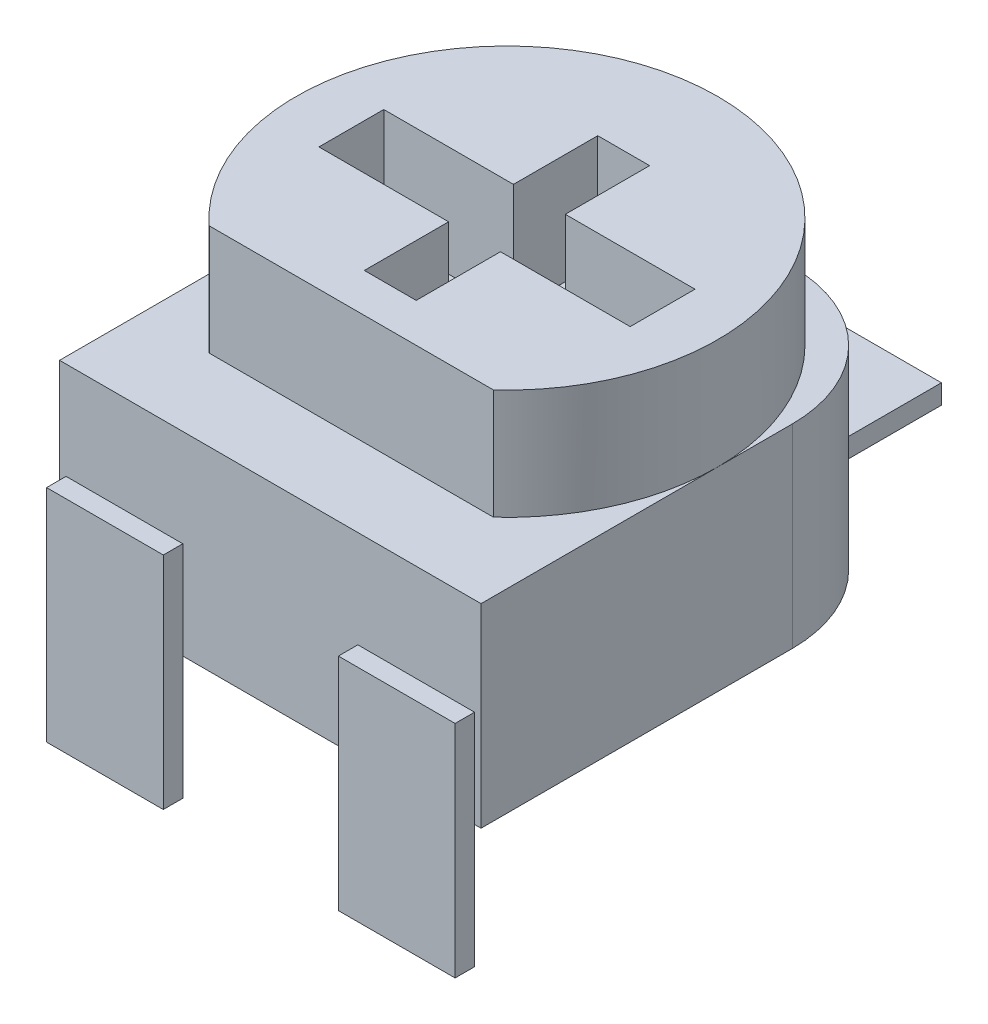
SolidWorks part; units mm, degrees
note: The reader was unsure of these and kept them because the rebuilt part matched: shared geometry of "草图1<3>", "草图1<4>".
ref_plane "前视基准面" through (0, 0, 0) normal (0, 0, 1) x (1, 0, 0)
ref_plane "上视基准面" through (0, 0, 0) normal (0, 1, 0) x (1, 0, 0)
ref_plane "右视基准面" through (0, 0, 0) normal (1, 0, 0) x (0, 0, -1)
other "Configuration Table"
sketch "草图1" plane through (0, 0, 0) normal (0, 1, 0) x (1, 0, 0)
  line L0 (-2.1915, -2.4) -> (2.1915, -2.4)
  line L1 (-3.25, 3.25) -> (3.25, 3.25)
  line L2 (-3.25, 3.25) -> (-3.25, -3.65)
  line L3 (-3.25, -3.65) -> (3.25, -3.65)
  line L4 (3.25, 3.25) -> (3.25, -3.65)
  line L5 (0, 3.25) -> (0, -3.65) construction
  line L6 (-2.4, -0.5) -> (2.4, -0.5)
  line L7 (-2.4, -0.5) -> (-2.4, 0.5)
  line L8 (-2.4, 0.5) -> (2.4, 0.5)
  line L9 (2.4, -0.5) -> (2.4, 0.5)
  line L10 (-2.4, -0.5) -> (2.4, 0.5) construction
  line L11 (-2.4, 0.5) -> (2.4, -0.5) construction
  line L12 (-0.4, -1.8) -> (0.4, -1.8)
  line L13 (-0.4, -1.8) -> (-0.4, 1.8)
  line L14 (-0.4, 1.8) -> (0.4, 1.8)
  line L15 (0.4, -1.8) -> (0.4, 1.8)
  line L16 (-0.4, -1.8) -> (0.4, 1.8) construction
  line L17 (-0.4, 1.8) -> (0.4, -1.8) construction
  circle A0 centre (0, 0) radius 3.25
  circle A1 centre (0, 0) radius 1.8
  dimension "D4" = 1.25
  dimension "D1" = 3.25
  dimension "D2" = 3.65
  dimension "D3" = 6.5
  dimension "D5" = 0.8
  dimension "D6" = 1
  dimension "D7" = 4.8
  dimension "D8" = 3.6
extrude "凸台-拉伸1" add sketch "草图1" along normal blind 3 contours L4 L3 L2 L1
extrude "凸台-拉伸2" add sketch "草图1<3>" along normal blind 1.7 from surface at 3 contours A0 | L6 L9 L8 L7 | L13 L14 L15 L12
sketch "草图1<3>" plane through (0, 0, 0) normal (0, 1, 0) x (1, 0, 0) same geometry as "草图1"
extrude "切除-拉伸1" cut sketch "草图1<4>" against normal up to surface (1.7 mm away) from surface at 4.7 contours L0 A0 up to face at (0, 3, 2.6375) starting at face at (0, 4.7, -3.25)
sketch "草图1<4>" plane through (0, 0, 0) normal (0, 1, 0) x (1, 0, 0) same geometry as "草图1"
fillet "圆角1" radius 2.1 2 edges at (3.25, 1.5, -3.25) (-3.25, 1.5, -3.25)
sketch "草图2" plane through (0, 0, 3.65) normal (0, 0, 1) x (1, 0, 0)
  line L0 (-3.25, 1.5) -> (3.25, 1.5)
  line L1 (-3.25, 3) -> (-3.25, 0) construction
  line L2 (3.25, 3) -> (3.25, 0) construction
  line L4 (-3.15, 1.5) -> (-1.35, 1.5)
  line L5 (-3.15, 1.5) -> (-3.15, -1.9)
  line L6 (-3.15, -1.9) -> (-1.35, -1.9)
  line L7 (-1.35, 1.5) -> (-1.35, -1.9)
  line L8 (1.35, 1.5) -> (3.15, 1.5)
  line L9 (1.35, 1.5) -> (1.35, -1.9)
  line L10 (1.35, -1.9) -> (3.15, -1.9)
  line L11 (3.15, 1.5) -> (3.15, -1.9)
  dimension "D1" = 0.1
  dimension "D2" = 0.1
  dimension "D3" = 1.8
  dimension "D4" = 1.8
  dimension "D5" = 3.4
  dimension "D6" = 3.4
extrude "凸台-拉伸3" add sketch "草图2" along normal blind 0.3 contours L5 L6 L7 L4 | L9 L10 L11 L8
sketch "草图3" plane through (0, 0, -3.25) normal (0, 0, -1) x (-1, 0, 0)
  line L0 (1.15, 0) -> (1.15, 3) construction
  line L1 (-1.15, 0) -> (1.15, 0)
  line L2 (-1.15, 0) -> (-1.15, 0.3)
  line L3 (-1.15, 0.3) -> (1.15, 0.3)
  line L4 (1.15, 0) -> (1.15, 0.3)
  dimension "D1" = 0.3
extrude "凸台-拉伸4" add sketch "草图3" along normal blind 2.3
